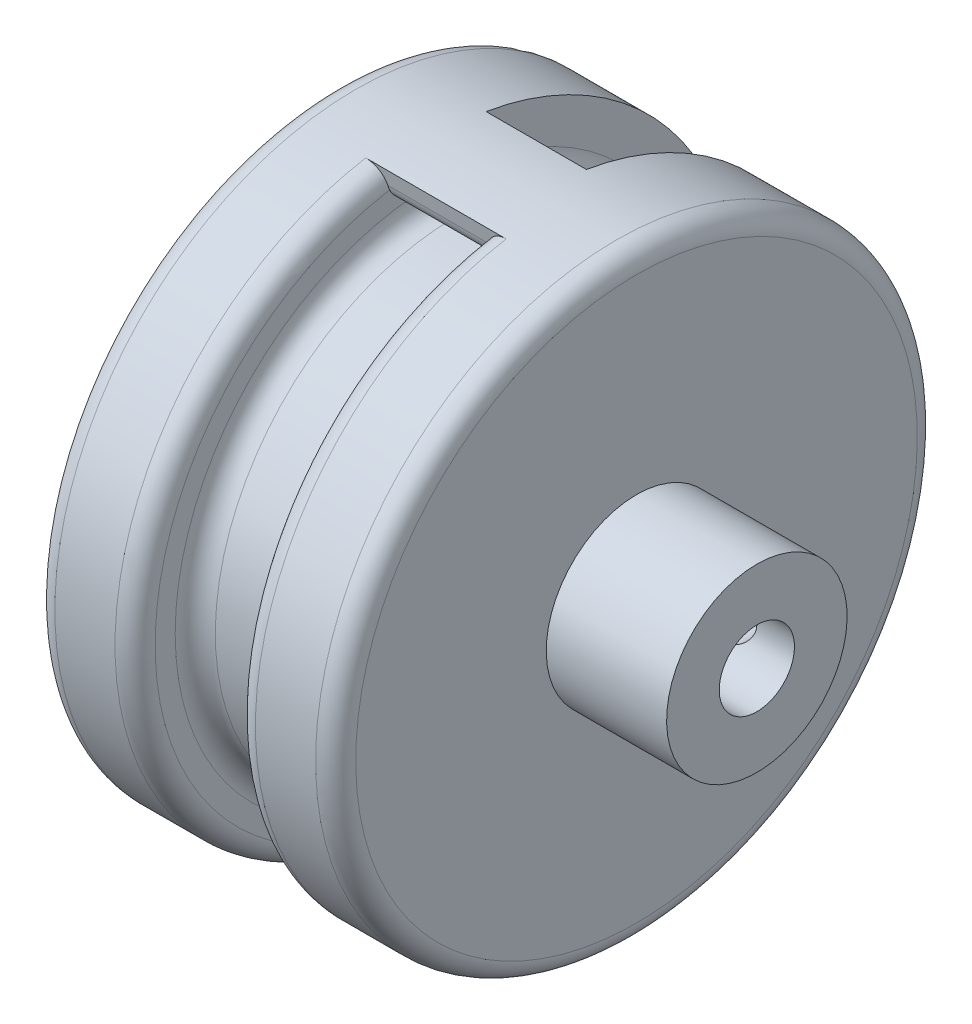
SolidWorks part; units mm, degrees
ref_plane "Plan de face" through (0, 0, 0) normal (0, 0, 1) x (1, 0, 0)
ref_plane "Plan de dessus" through (0, 0, 0) normal (0, 1, 0) x (1, 0, 0)
ref_plane "Plan de droite" through (0, 0, 0) normal (1, 0, 0) x (0, 0, -1)
sketch "Sketch1" plane through (0, 0, 0) normal (0, 0, 1) x (1, 0, 0)
  line L0 (-15, 0) -> (-15, 30)
  line L1 (-15, 30) -> (-5, 30)
  line L2 (-5, 30) -> (-5, 24)
  line L3 (-5, 24) -> (5, 24)
  line L4 (5, 24) -> (5, 30)
  line L5 (5, 30) -> (15, 30)
  line L6 (15, 30) -> (15, 0)
  line L7 (15, 0) -> (-15, 0)
  point P2 (0, 0)
  dimension "D1" = 30
  dimension "D2" = 10
  dimension "D3" = 10
  dimension "D4" = 6
  dimension "D5" = 6
revolve "Revolve1" add sketch "Sketch1" angle 360 about L7
sketch "Sketch2" plane through (15, 0, 0) normal (1, 0, 0) x (0, 0, -1)
  circle A0 centre (0, 0) radius 9
  dimension "D1" = 18
extrude "Boss-Extrude1" add sketch "Sketch2" along normal blind 12
sketch "Sketch3" plane through (27, 0, 0) normal (1, 0, 0) x (0, 0, -1)
  circle A0 centre (0, 0) radius 3.75
  dimension "D1" = 7.5
extrude "Cut-Extrude1" cut sketch "Sketch3" against normal through all and the other way through all
sketch "Sketch4" plane through (0, 0, 0) normal (0, 0, 1) x (1, 0, 0)
  line L0 (27, 0) -> (15, 0) construction
  line L1 (27, -9) -> (27, 9) construction
  line L2 (15, -30) -> (15, 30) construction
  circle A0 centre (21, 0) radius 2.25
  point P8 (0, 0)
  point P9 (21, 0)
  dimension "D1" = 4.5
extrude "Cut-Extrude2" cut sketch "Sketch4" against normal blind 12
sketch "Sketch6" plane through (15, 0, 0) normal (1, 0, 0) x (0, 0, -1)
  line L0 (-5, 29.5804) -> (-4.4239, 26.172)
  line L1 (5, 29.5804) -> (4.4239, 26.172)
  arc A0 (-5, 29.5804) -> (5, 29.5804) centre (0, 0) cw
  circle A1 centre (0, 0) radius 30 construction
  arc A2 (-4.4239, 26.172) -> (4.4239, 26.172) centre (0, -3.5) cw
  point P9 (0, 30)
  point P10 (6.7597, 29.2285)
  dimension "D1" = 30
  dimension "D2" = 30
  dimension "D3" = 3.5
  dimension "D4" = 10
extrude "Boss-Extrude3" add sketch "Sketch6" against normal up to surface (30 mm away) up to face at (-15, 3.75, 0)
mirror "Mirror1" about plane through (0, 0, 0) normal (0, 1, 0) of "Boss-Extrude3"
fillet "Fillet1" radius 2 6 edges at (15, 30, 0) (5, 0, 30) (5, 24, 0) (-5, 24, 0) (-5, 0, 30) (-15, 30, 0)
fillet "Fillet2" radius 2 4 edges at (0, -26.172, -4.4239) (0, -26.172, 4.4239) (0, 26.172, -4.4239) (0, 26.172, 4.4239)
